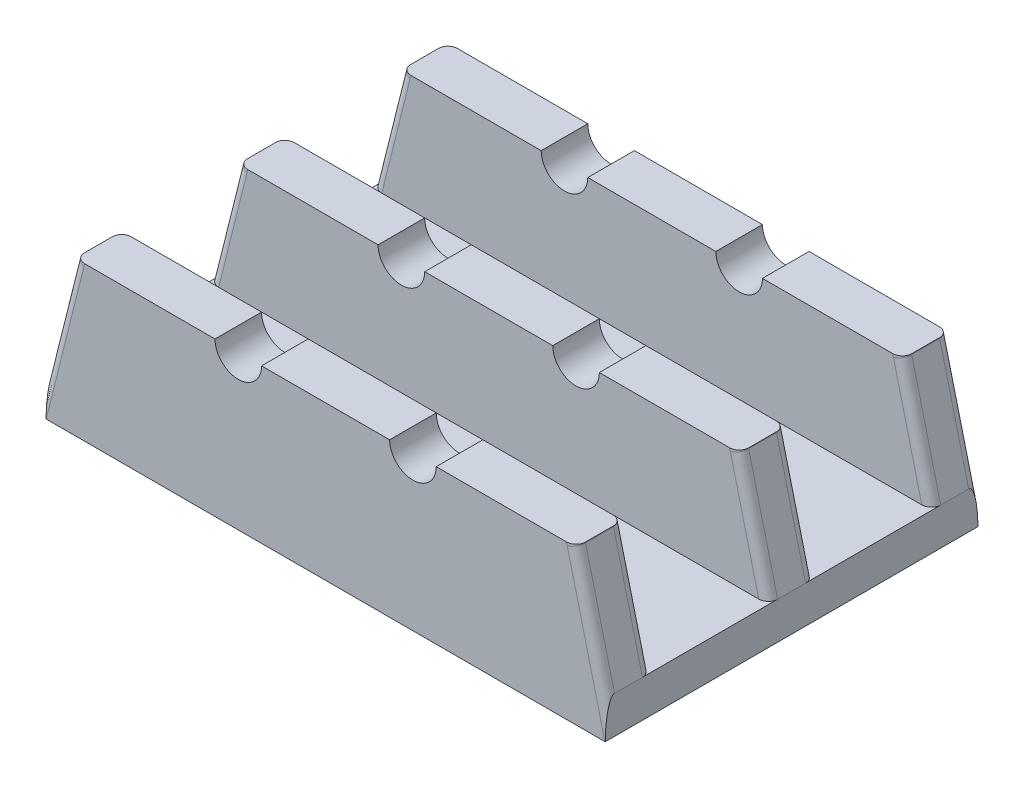
SolidWorks part; units mm, degrees
ref_plane "Front Plane" through (0, 0, 0) normal (0, 0, 1) x (1, 0, 0)
ref_plane "Top Plane" through (0, 0, 0) normal (0, 1, 0) x (1, 0, 0)
ref_plane "Right Plane" through (0, 0, 0) normal (1, 0, 0) x (0, 0, -1)
sketch "Sketch1" plane through (0, 0, 0) normal (0, 1, 0) x (1, 0, 0)
  line L1 (-9.75, -14.75) -> (9.75, -14.75)
  line L2 (-9.75, -14.75) -> (-9.75, 14.75)
  line L3 (-9.75, 14.75) -> (9.75, 14.75)
  line L4 (9.75, -14.75) -> (9.75, 14.75)
  line L5 (-9.75, -14.75) -> (9.75, 14.75) construction
  line L6 (-9.75, 14.75) -> (9.75, -14.75) construction
  point P0 (0, 0)
  dimension "D1" = 19.5
  dimension "D2" = 29.5
extrude "Boss-Extrude1" add sketch "Sketch1" along normal blind 4 contours L2 L1 L4 L3
sketch "Sketch2" plane through (0, 4, 0) normal (0, 1, 0) x (1, 0, 0)
  line L1 (-30, -20) -> (30, -20)
  line L2 (-30, -20) -> (-30, 20)
  line L3 (-30, 20) -> (30, 20)
  line L4 (30, -20) -> (30, 20)
  line L5 (-30, -20) -> (30, 20) construction
  line L6 (-30, 20) -> (30, -20) construction
  point P0 (0, 0)
  dimension "D1" = 60
  dimension "D2" = 40
extrude "Boss-Extrude3" add sketch "Sketch2" along normal blind 4
sketch "Sketch3" plane through (0, 8, 0) normal (0, 1, 0) x (1, 0, 0)
  line L0 (30, -20) -> (30, 20) construction
  line L1 (-30, 20) -> (30, 20)
  line L2 (-30, 20) -> (-30, 15)
  line L3 (-30, 15) -> (30, 15)
  line L4 (30, 20) -> (30, 15)
  line L6 (30, -20) -> (30, -15)
  line L7 (-30, -15) -> (30, -15)
  line L8 (-30, -20) -> (-30, -15)
  line L9 (-30, -20) -> (30, -20)
  line M9 (30, -20) -> (30, 20)
  line M10 (30, 20) -> (-30, 20)
  line M11 (-30, 20) -> (-30, -20)
  dimension "D1" = 5
extrude "Boss-Extrude4" add sketch "Sketch3" along normal blind 20 contours L3 M11 M9 M10 | L6 L7 L8 L9
chamfer "Chamfer1" distance 5 distance2 20 1 edges at (-30, 28, 17.5) first distance on face at (0, 28, 17.5)
chamfer "Chamfer2" distance 20 distance2 5 1 edges at (-30, 28, -17.5) first distance on face at (-30, 12.5714, -2.1429)
chamfer "Chamfer3" distance 20 distance2 5 2 edges at (30, 28, -17.5) (30, 28, 17.5) first distance on face at (30, 17, 0)
fillet "Fillet1" radius 10 4 edges at (25, 28, 17.5) (25, 28, -17.5) (-25, 28, 17.5) (-25, 28, -17.5)
fillet "Fillet2" radius 1 10 edges at (28.4468, 14.2127, -20) (23.3464, 25.8821, -20) (-28.4468, 14.2127, -20) (-23.3464, 25.8821, -20) (-28.4468, 14.2127, 20) (-23.3464, 25.8821, 20) (28.4468, 14.2127, 20) (23.3464, 25.8821, 20) (0, 28, -20) (0, 28, 20)
sketch "Sketch4" plane through (0, 8, 0) normal (0, 1, 0) x (1, 0, 0)
  line L0 (30, -15) -> (30, 15) construction
  line L1 (-30, 2.5) -> (30, 2.5)
  line L2 (-30, 2.5) -> (-30, -2.5)
  line L3 (-30, -2.5) -> (30, -2.5)
  line L4 (30, 2.5) -> (30, -2.5)
  line L5 (-30, 2.5) -> (30, -2.5) construction
  line L6 (-30, -2.5) -> (30, 2.5) construction
  point P0 (0, 0)
  dimension "D1" = 5
extrude "Boss-Extrude5" add sketch "Sketch4" along normal blind 20
chamfer "Chamfer4" distance 20 distance2 5 2 edges at (30, 28, 0) (-30, 28, 0) first distance on face at (30, 11.3671, 0) first distance on face at (-30, 11.3671, 0)
fillet "Fillet3" radius 10 2 edges at (-25, 28, 0) (25, 28, 0)
fillet "Fillet4" radius 1 10 edges at (28.4468, 14.2127, -2.5) (23.3464, 25.8821, -2.5) (-28.4468, 14.2127, -2.5) (-23.3464, 25.8821, -2.5) (-28.4468, 14.2127, 2.5) (-23.3464, 25.8821, 2.5) (28.4468, 14.2127, 2.5) (23.3464, 25.8821, 2.5) (0, 28, -2.5) (0, 28, 2.5)
fillet "Fillet5" radius 1 10 edges at (-28.4468, 14.2127, 15) (-23.3464, 25.8821, 15) (28.4468, 14.2127, 15) (23.3464, 25.8821, 15) (-28.4468, 14.2127, -15) (-23.3464, 25.8821, -15) (28.4468, 14.2127, -15) (23.3464, 25.8821, -15) (0, 28, 15) (0, 28, -15)
sketch "Sketch5" plane through (0, 0, 20) normal (0, 0, 1) x (1, 0, 0)
  line L0 (17.1922, 27) -> (-17.1922, 27) construction
  circle A0 centre (-9.3692, 20.5) radius 2.5
  circle A1 centre (9.3692, 20.5) radius 2.5
  dimension "D1" = 6.5
  dimension "D2" = 20.6
extrude "Cut-Extrude1" cut sketch "Sketch5" against normal through all contours A0 | A1
ref_plane "Plane1" through (0, 28, 0) normal (0, 1, 0) x (1, 0, 0)
sketch "Sketch6" plane through (0, 28, 0) normal (0, 1, 0) x (1, 0, 0)
  line L1 (-35.685, 22.7735) -> (35.685, 22.7735)
  line L2 (-35.685, 22.7735) -> (-35.685, -22.7735)
  line L3 (-35.685, -22.7735) -> (35.685, -22.7735)
  line L4 (35.685, 22.7735) -> (35.685, -22.7735)
  line L5 (-35.685, 22.7735) -> (35.685, -22.7735) construction
  line L6 (-35.685, -22.7735) -> (35.685, 22.7735) construction
  point P0 (0, 0)
extrude "Cut-Extrude2" cut sketch "Sketch6" against normal blind 7.5
